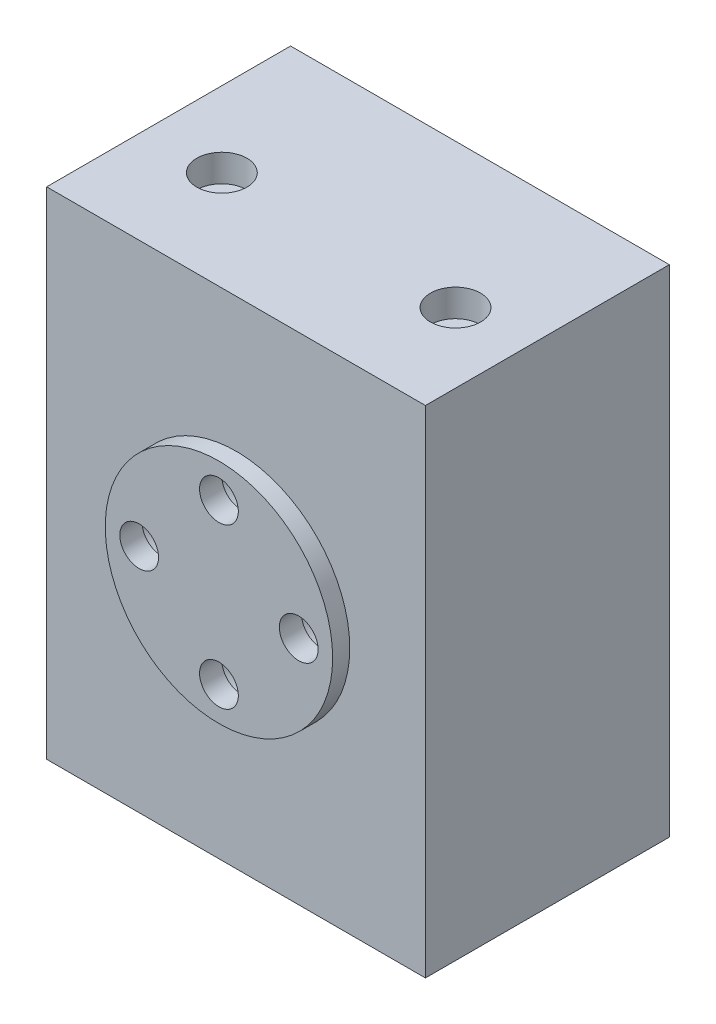
SolidWorks part; units mm, degrees
ref_plane "Front Plane" through (0, 0, 0) normal (0, 0, 1) x (1, 0, 0)
ref_plane "Top Plane" through (0, 0, 0) normal (0, 1, 0) x (1, 0, 0)
ref_plane "Right Plane" through (0, 0, 0) normal (1, 0, 0) x (0, 0, -1)
sketch "Sketch1" plane through (0, 0, 0) normal (0, 0, 1) x (1, 0, 0)
  circle A0 centre (0, 0) radius 9.975
  dimension "D1" = 19.95
extrude "Boss-Extrude1" add sketch "Sketch1" along normal blind 1.5
sketch "Sketch3" plane through (0, 0, 0) normal (0, 0, -1) x (-1, 0, 0)
  line L0 (16.615, 21.75) -> (16.615, -21.75)
  line L1 (-12.615, 17.75) -> (12.615, 17.75)
  line L2 (-12.615, 17.75) -> (-12.615, -17.75)
  line L3 (-12.615, -17.75) -> (12.615, -17.75)
  line L4 (12.615, 17.75) -> (12.615, -17.75)
  line L5 (-12.615, 17.75) -> (12.615, -17.75) construction
  line L6 (-12.615, -17.75) -> (12.615, 17.75) construction
  line L7 (-16.615, -21.75) -> (16.615, -21.75)
  line L8 (-16.615, 21.75) -> (-16.615, -21.75)
  line L9 (-16.615, 21.75) -> (16.615, 21.75)
  point P0 (0, 0)
  dimension "D1" = 35.5
  dimension "D2" = 25.23
  dimension "D3" = 4
extrude "Boss-Extrude4" add sketch "Sketch3" along normal blind 2.65 contours L2 L1 L4 L3
extrude "Boss-Extrude5" add sketch "Sketch3<5>" along normal blind 21.4
sketch "Sketch3<5>" plane through (0, 0, 0) normal (0, 0, -1) x (-1, 0, 0) same geometry as "Sketch3"
sketch "Sketch4" plane through (0, 0, -2.65) normal (0, 0, -1) x (-1, 0, 0)
  line L1 (12.615, 17.75) -> (7.415, 17.75)
  line L2 (12.615, 17.75) -> (12.615, 16.65)
  line L3 (12.615, 16.65) -> (7.415, 16.65)
  line L4 (7.415, 17.75) -> (7.415, 16.65)
  line L5 (-12.615, 17.75) -> (-7.415, 17.75)
  line L6 (-12.615, 17.75) -> (-12.615, 16.65)
  line L7 (-12.615, 16.65) -> (-7.415, 16.65)
  line L8 (-7.415, 17.75) -> (-7.415, 16.65)
  line L9 (12.615, -17.75) -> (9.415, -17.75)
  line L10 (12.615, -17.75) -> (12.615, -16.25)
  line L11 (12.615, -16.25) -> (9.415, -16.25)
  line L12 (9.415, -17.75) -> (9.415, -16.25)
  line L13 (-12.615, -17.75) -> (-9.415, -17.75)
  line L14 (-12.615, -17.75) -> (-12.615, -16)
  line L15 (-12.615, -16) -> (-9.415, -16)
  line L16 (-9.415, -17.75) -> (-9.415, -16)
  dimension "D1" = 1.1
  dimension "D2" = 5.2
  dimension "D3" = 5.2
  dimension "D4" = 1.1
  dimension "D5" = 3.2
  dimension "D6" = 1.5
  dimension "D7" = 3.2
extrude "Boss-Extrude6" add sketch "Sketch4" along normal blind 18.9 contours L2 L1 L4 L3 | L6 L5 L8 L7 | L10 L9 L12 L11 | L14 L13 L16 L15
sketch "Sketch6" plane through (0, 0, -2.65) normal (0, 0, -1) x (-1, 0, 0)
  line L1 (9.415, -17.75) -> (-9.415, -17.75)
  line L2 (9.415, -17.75) -> (9.415, -16)
  line L3 (9.415, -16) -> (-9.415, -16)
  line L4 (-9.415, -17.75) -> (-9.415, -16)
extrude "Boss-Extrude7" add sketch "Sketch6" along normal blind 5.3
sketch "Sketch2" plane through (0, 0, 1.5) normal (0, 0, 1) x (1, 0, 0)
  circle A0 centre (0, 0) radius 7 construction
  circle A1 centre (7, 0) radius 1.6
  circle A2 centre (0, -7) radius 1.6
  circle A3 centre (-7, 0) radius 1.6
  circle A4 centre (0, 7) radius 1.6
  point P14 (0, 0)
  dimension "D1" = 14
  dimension "D2" = 3.2
  dimension "D3" = 4
extrude "Cut-Extrude1" cut sketch "Sketch2" against normal blind 37
hole_wizard "CBORE for M3 Hex Socket Head Cap Screw1" positions "Sketch7" profile "Sketch8" counterbore size "M3" standard "ISO" end condition up to next
sketch "Sketch7" plane through (0, 0, -2.65) normal (0, 0, -1) x (-1, 0, 0)
  point P0 (0, 7)
  point P3 (-7, 0)
  point P6 (0, -7)
  point P9 (7, 0)
sketch "Sketch8" plane through (0, 7, -2.65) normal (1, 0, 0) x (0, 1, 0)
  line L0 (0, 0) -> (0, 4.15)
  line L1 (0, 4.15) -> (1.7, 4.15)
  line L3 (1.7, 4.15) -> (1.7, 2.2)
  line L4 (1.7, 2.2) -> (2.9, 2.2)
  line L5 (2.9, 2.2) -> (2.9, 0)
  line L7 (2.9, 0) -> (0, 0)
  line L11 (0, -6.35) -> (0, 107.95) construction
  dimension "Thru Hole Dia." = 3.4
  dimension "Thru Hole Depth" = 4.15
  dimension "C'Bore Dia." = 5.8
  dimension "C'Bore Depth" = 2.2
hole_wizard "CBORE for M2 Hex Socket Head Cap Screw1" positions "Sketch10" profile "Sketch11" counterbore size "M2" standard "ISO"
sketch "Sketch10" plane through (0, -21.75, 0) normal (0, -1, 0) x (1, 0, 0)
  point P0 (-10.005, -5.01)
  point P3 (10.495, -5.01)
sketch "Sketch11" plane through (-10.005, -21.75, -5.01) normal (1, 0, 0) x (0, 0, -1)
  line L0 (0, 0) -> (0, 7.221)
  line L1 (0, 7.221) -> (1.2, 6.5)
  line L2 (1.2, 6.5) -> (1.2, 2.4)
  line L3 (1.2, 2.4) -> (2.2, 2.4)
  line L4 (2.2, 2.4) -> (2.2, 0)
  line L5 (2.2, 0) -> (0, 0)
  line L10 (0, 7.221) -> (-1.2, 6.5) construction
  line L11 (0, -6.35) -> (0, 107.95) construction
  dimension "Hole Dia." = 2.4
  dimension "Hole Depth" = 6.5
  dimension "C'Bore Dia." = 4.4
  dimension "C'Bore Depth" = 2.4
  dimension "Drill Angle" = 118
hole_wizard "CBORE for M2 Hex Socket Head Cap Screw2" positions "Sketch12" profile "Sketch13" counterbore size "M2" standard "ISO"
sketch "Sketch12" plane through (0, 21.75, 0) normal (0, 1, 0) x (1, 0, 0)
  point P0 (-10.005, 8.76)
  point P3 (10.495, 8.76)
sketch "Sketch13" plane through (-10.005, 21.75, -8.76) normal (1, 0, 0) x (0, 0, 1)
  line L0 (0, 0) -> (0, 7.221)
  line L1 (0, 7.221) -> (1.2, 6.5)
  line L2 (1.2, 6.5) -> (1.2, 2.4)
  line L3 (1.2, 2.4) -> (2.2, 2.4)
  line L4 (2.2, 2.4) -> (2.2, 0)
  line L5 (2.2, 0) -> (0, 0)
  line L10 (0, 7.221) -> (-1.2, 6.5) construction
  line L11 (0, -6.35) -> (0, 107.95) construction
  dimension "Hole Dia." = 2.4
  dimension "Hole Depth" = 6.5
  dimension "C'Bore Dia." = 4.4
  dimension "C'Bore Depth" = 2.4
  dimension "Drill Angle" = 118
